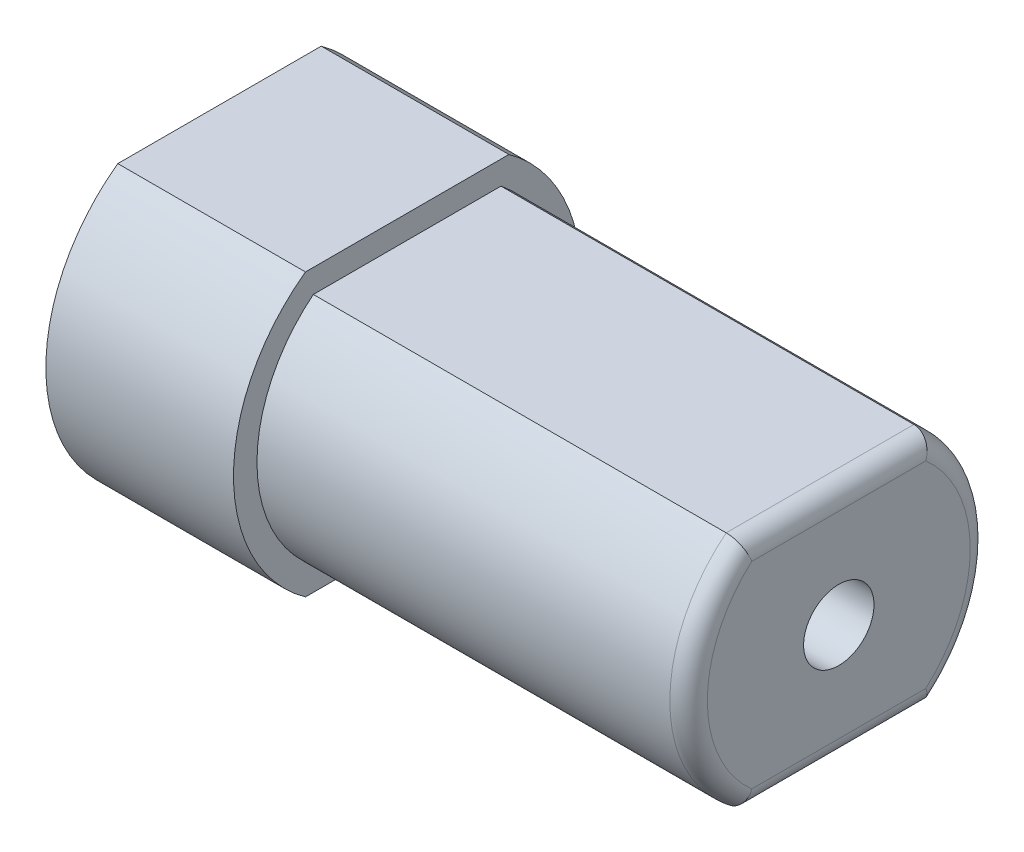
SolidWorks part; units mm, degrees
ref_plane "Front Plane" through (0, 0, 0) normal (0, 0, 1) x (1, 0, 0)
ref_plane "Top Plane" through (0, 0, 0) normal (0, 1, 0) x (1, 0, 0)
ref_plane "Right Plane" through (0, 0, 0) normal (1, 0, 0) x (0, 0, -1)
sketch "Sketch1" plane through (0, 0, 0) normal (1, 0, 0) x (0, 0, -1)
  line L1 (-12.7, -15.875) -> (12.7, -15.875)
  line L3 (-12.7, 15.875) -> (12.7, 15.875)
  line L5 (0, 0) -> (12.7, 15.875) construction
  line L6 (-12.7, 15.875) -> (0, 0) construction
  arc A0 (-12.7, 15.875) -> (-12.7, -15.875) centre (0, 0) ccw
  arc A1 (12.7, -15.875) -> (12.7, 15.875) centre (0, 0) ccw
  point P0 (0, 0)
  dimension "D3" = 20.3299
  dimension "D1" = 25.4
  dimension "D2" = 31.75
extrude "Boss-Extrude1" add sketch "Sketch1" along normal blind 58.42 contours L3 A1 L1 A0
sketch "Sketch2" plane through (58.42, 0, 0) normal (1, 0, 0) x (0, 0, -1)
  circle A0 centre (0, 0) radius 4.7625
  dimension "D1" = 9.525
extrude "Cut-Extrude1" cut sketch "Sketch2" against normal blind 25.4
sketch "Sketch4" plane through (0, 0, 0) normal (-1, 0, 0) x (0, 0, 1)
  line L0 (-13.7688, -19.05) -> (13.7688, -19.05)
  line L1 (13.7688, 19.05) -> (-13.7688, 19.05)
  line L2 (12.7, 15.875) -> (-12.7, 15.875)
  line L3 (-12.7, -15.875) -> (12.7, -15.875)
  line L4 (12.7, 15.875) -> (-12.7, 15.875) construction
  line L5 (-12.7, -15.875) -> (12.7, -15.875) construction
  arc A0 (-13.7688, 19.05) -> (-13.7688, -19.05) centre (0, 0) ccw
  arc A1 (13.7688, -19.05) -> (13.7688, 19.05) centre (0, 0) ccw
  arc A2 (12.7, -15.875) -> (12.7, 15.875) centre (0, 0) ccw
  arc A3 (-12.7, 15.875) -> (-12.7, -15.875) centre (0, 0) ccw
  arc A4 (12.7, -15.875) -> (12.7, 15.875) centre (0, 0) ccw construction
  arc A5 (-12.7, 15.875) -> (-12.7, -15.875) centre (0, 0) ccw construction
  dimension "D1" = 0
  dimension "D2" = 3.175
extrude "Boss-Extrude2" add sketch "Sketch4" along normal blind 25.4
fillet "Fillet1" radius 2.54 4 edges at (58.42, 0, -20.3299) (58.42, 15.875, 0) (58.42, 0, 20.3299) (58.42, -15.875, 0)
